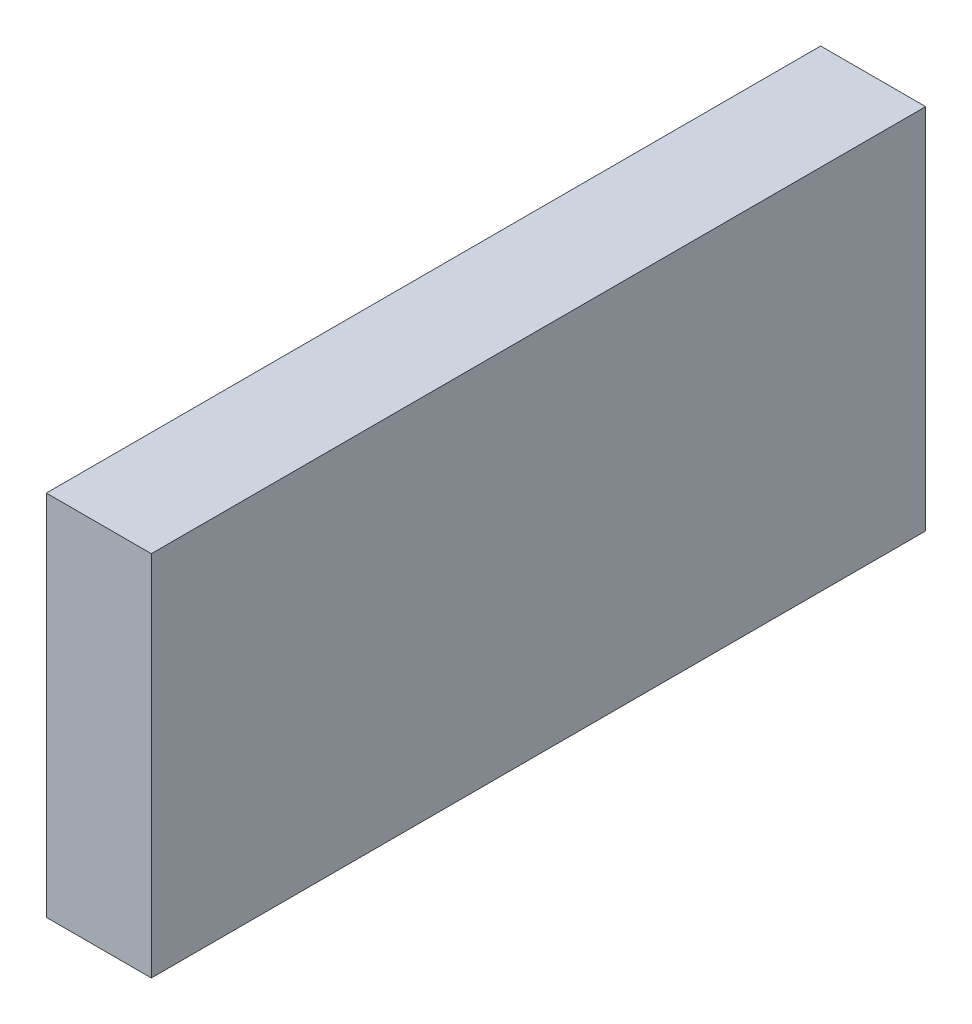
SolidWorks part; units mm, degrees
ref_plane "Front Plane" through (0, 0, 0) normal (0, 0, 1) x (1, 0, 0)
ref_plane "Top Plane" through (0, 0, 0) normal (0, 1, 0) x (1, 0, 0)
ref_plane "Right Plane" through (0, 0, 0) normal (1, 0, 0) x (0, 0, -1)
sketch "Sketch1" plane through (0, 0, 0) normal (1, 0, 0) x (0, 0, -1)
  line L1 (147.5, -70) -> (-147.5, -70)
  line L2 (147.5, -70) -> (147.5, 70)
  line L3 (147.5, 70) -> (-147.5, 70)
  line L4 (-147.5, -70) -> (-147.5, 70)
  line L5 (147.5, -70) -> (-147.5, 70) construction
  line L6 (147.5, 70) -> (-147.5, -70) construction
  point P0 (0, 0)
  dimension "D1" = 295
  dimension "D2" = 140
extrude "Boss-Extrude1" add sketch "Sketch1" along normal blind 40
